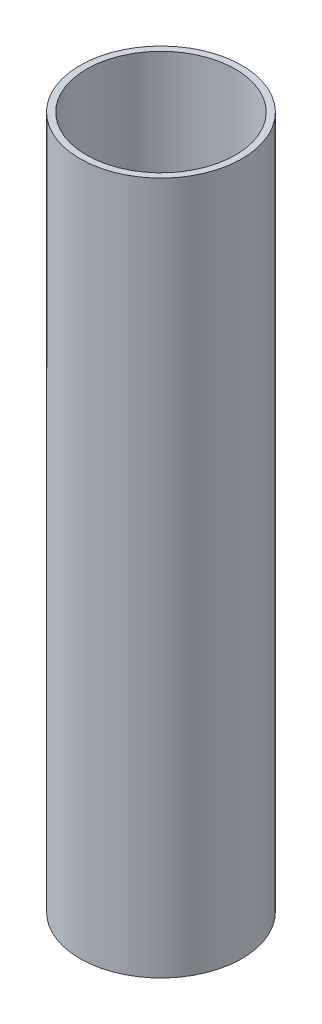
SolidWorks part; units mm, degrees
material "ПВХ 0.007 Смягченный"
ref_plane "Спереди" through (0, 0, 0) normal (0, 0, 1) x (1, 0, 0)
ref_plane "Сверху" through (0, 0, 0) normal (0, 1, 0) x (1, 0, 0)
ref_plane "Справа" through (0, 0, 0) normal (1, 0, 0) x (0, 0, -1)
sketch "Эскиз1" plane through (0, 0, 0) normal (0, 1, 0) x (1, 0, 0)
  circle A0 centre (0, 0) radius 25
  circle A1 centre (0, 0) radius 23
  dimension "ExDBody" = 50
  dimension "InDBody" = 46
extrude "Бобышка-Вытянуть1" add sketch "Эскиз1" along normal blind 214
